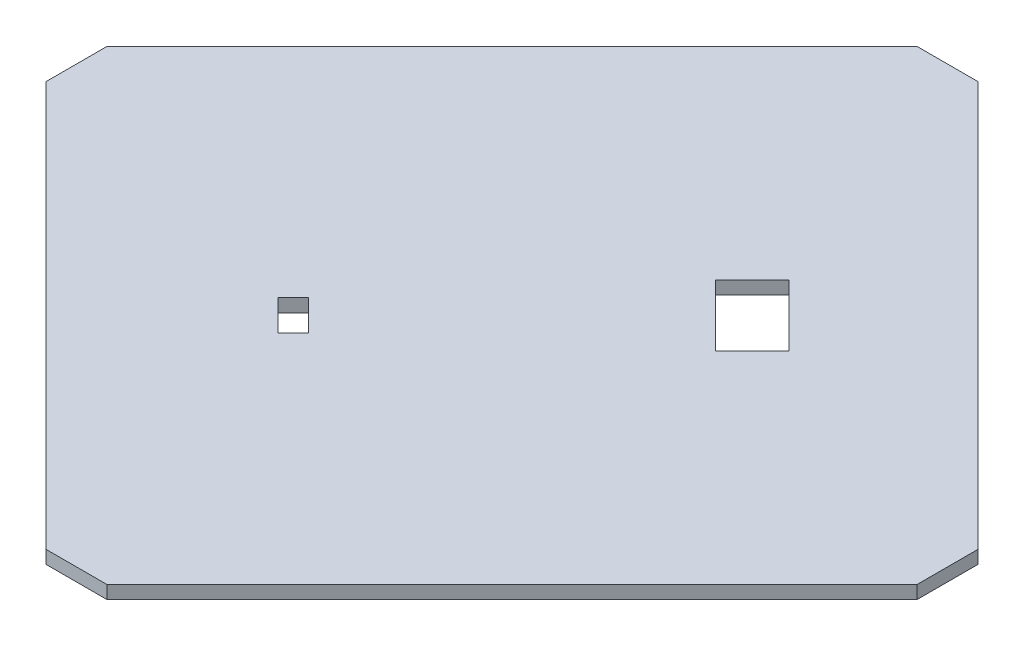
SolidWorks part; units mm, degrees
other "Top Plate"
ref_plane "Front Plane" through (0, 0, 0) normal (0, 0, 1) x (1, 0, 0)
ref_plane "Top Plane" through (0, 0, 0) normal (0, 1, 0) x (1, 0, 0)
ref_plane "Right Plane" through (0, 0, 0) normal (1, 0, 0) x (0, 0, -1)
sketch "Sketch1" plane through (0, 0, 0) normal (0, 1, 0) x (1, 0, 0)
  line L0 (-7, 100) -> (7, 100)
  line L1 (7, 100) -> (100, 7)
  line L2 (100, 7) -> (100, -7)
  line L3 (100, -7) -> (7, -100)
  line L4 (7, -100) -> (-7, -100)
  line L5 (-7, -100) -> (-100, -7)
  line L6 (-100, -7) -> (-100, 7)
  line L7 (-100, 7) -> (-7, 100)
  point P6 (0, 0)
  point P10 (0, 0)
  point P11 (0, 100)
  point P13 (100, 0)
  dimension "D1" = 200
  dimension "D2" = 200
  dimension "D3" = 14
extrude "Main Plate" add sketch "Sketch1" along normal blind 3 contours L1 L2 L3 L4 L5 L6 L7 L0
sketch "Sketch2" plane through (0, 0, 0) normal (0, -1, 0) x (1, 0, 0)
  line L0 (8.8388, 15.9099) -> (15.9099, 8.8388)
  line L3 (15.9099, 8.8388) -> (18.0312, 10.9602)
  line L6 (18.0312, 10.9602) -> (10.9602, 18.0312)
  line L7 (10.9602, 18.0312) -> (8.8388, 15.9099)
  line L8 (0, 0) -> (53.5, 53.5) construction
  line L9 (100, 7) -> (7, 100) construction
  line L10 (15.9099, -8.8388) -> (8.8388, -15.9099)
  line L11 (10.9602, -18.0312) -> (18.0312, -10.9602)
  line L12 (18.0312, -10.9602) -> (15.9099, -8.8388)
  line L13 (8.8388, -15.9099) -> (10.9602, -18.0312)
  line L14 (-8.8388, -15.9099) -> (-15.9099, -8.8388)
  line L15 (-18.0312, -10.9602) -> (-10.9602, -18.0312)
  line L16 (-10.9602, -18.0312) -> (-8.8388, -15.9099)
  line L17 (-15.9099, -8.8388) -> (-18.0312, -10.9602)
  line L18 (-15.9099, 8.8388) -> (-8.8388, 15.9099)
  line L19 (-10.9602, 18.0312) -> (-18.0312, 10.9602)
  line L20 (-18.0312, 10.9602) -> (-15.9099, 8.8388)
  line L21 (-8.8388, 15.9099) -> (-10.9602, 18.0312)
  point P8 (14.4957, 14.4957)
  point P9 (12.3744, 12.3744)
  point P26 (0, 0)
  dimension "D1" = 3
  dimension "D2" = 10
  dimension "D3" = 17.5
  dimension "D4" = 4
extrude "Bottom Plate Connectors" add sketch "Sketch2" along normal blind 22
fillet "Remove Stress Concentrations" radius 2.5 12 edges at (-14.4957, 0, -14.4957) (-16.9706, 0, -9.8995) (-16.9706, 0, 9.8995) (9.8995, 0, 16.9706) (-14.4957, 0, 14.4957) (-9.8995, 0, 16.9706) (14.4957, 0, 14.4957) (16.9706, 0, -9.8995) (16.9706, 0, 9.8995) (-9.8995, 0, -16.9706) (14.4957, 0, -14.4957) (9.8995, 0, -16.9706)
sketch "Sketch3" plane through (0, 0, 0) normal (0, -1, 0) x (1, 0, 0)
  line L0 (30.4056, -16.2635) -> (38.8909, -24.7487)
  line L1 (38.8909, -24.7487) -> (24.7487, -38.8909)
  line L2 (24.7487, -38.8909) -> (16.2635, -30.4056)
  line L3 (16.2635, -30.4056) -> (30.4056, -16.2635)
  line L4 (16.2635, -16.2635) -> (53.5, -53.5) construction
  line L5 (21.5668, -10.9602) -> (10.9602, -21.5668) construction
  line L6 (7, -100) -> (100, -7) construction
  line L7 (-23.3345, 30.4056) -> (-19.799, 26.8701)
  line L8 (-19.799, 26.8701) -> (-26.8701, 19.799)
  line L9 (-26.8701, 19.799) -> (-30.4056, 23.3345)
  line L10 (-30.4056, 23.3345) -> (-23.3345, 30.4056)
  line L11 (-16.2635, 16.2635) -> (-53.5, 53.5) construction
  line L12 (-21.5668, 10.9602) -> (-10.9602, 21.5668) construction
  line L13 (-7, 100) -> (-100, 7) construction
  point P10 (23.3345, -23.3345)
  point P21 (-23.3345, 23.3345)
  dimension "D1" = 20
  dimension "D2" = 12
  dimension "D3" = 10
  dimension "D4" = 10
  dimension "D5" = 5
  dimension "D6" = 10
extrude "Wire Holes" cut sketch "Sketch3" against normal through all
